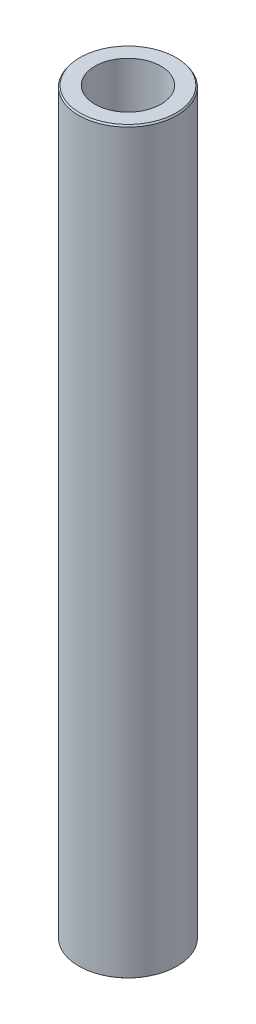
SolidWorks part; units mm, degrees
ref_plane "Front Plane" through (0, 0, 0) normal (0, 0, 1) x (1, 0, 0)
ref_plane "Top Plane" through (0, 0, 0) normal (0, 1, 0) x (1, 0, 0)
ref_plane "Right Plane" through (0, 0, 0) normal (1, 0, 0) x (0, 0, -1)
sketch "Sketch1" plane through (0, 0, 0) normal (0, 1, 0) x (1, 0, 0)
  circle A0 centre (0, 0) radius 15
  dimension "SHAFT_OD" = 30
extrude "Boss-Extrude1" add sketch "Sketch1" along normal blind 225.4345
sketch "Sketch2" plane through (0, 0, 0) normal (0, 1, 0) x (1, 0, 0)
  circle A0 centre (0, 0) radius 10.0659
  dimension "BORE_D" = 20.1318
extrude "Cut-Extrude1" cut sketch "Sketch2" along normal through all
chamfer "Chamfer1" distance 0.4667 angle 37.293 2 edges at (0, 225.4345, 15) (0, 0, 15) first distance on face at (0, 225.4345, 15) first distance on face at (0, 0, 10.0659)
